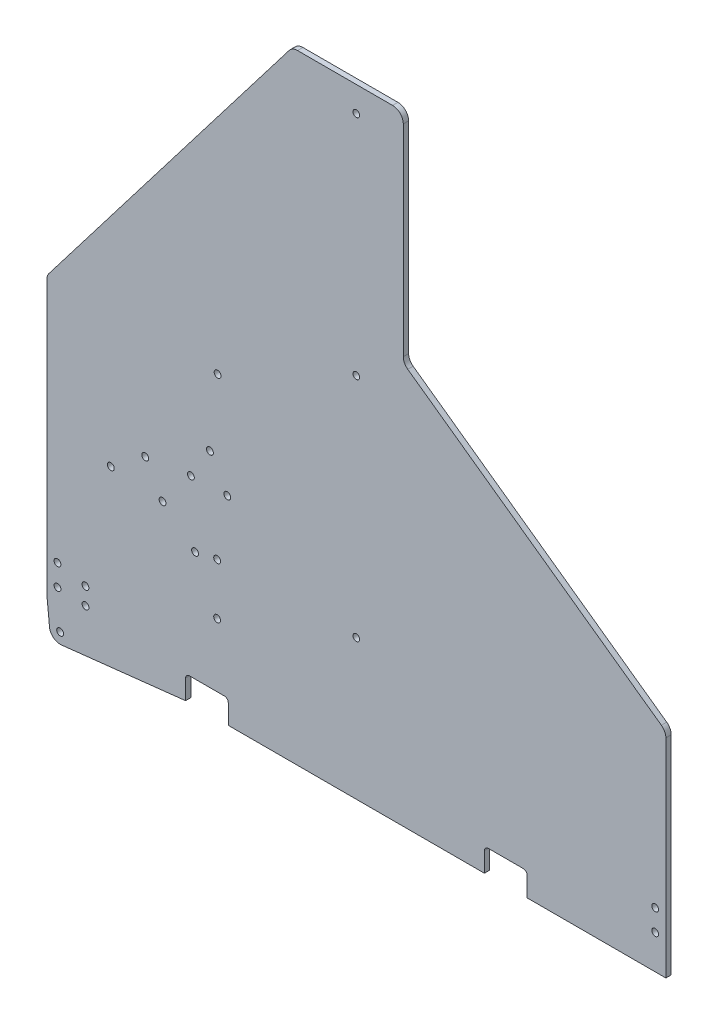
SolidWorks part; units mm, degrees
ref_plane "Front Plane" through (0, 0, 0) normal (0, 0, 1) x (1, 0, 0)
ref_plane "Top Plane" through (0, 0, 0) normal (0, 1, 0) x (1, 0, 0)
ref_plane "Right Plane" through (0, 0, 0) normal (1, 0, 0) x (0, 0, -1)
sketch "Sketch1" plane through (0, 0, 0) normal (0, 0, 1) x (1, 0, 0)
  line L0 (82.55, -20.32) -> (82.55, -6.35)
  line L2 (0, 0) -> (0, 157.48)
  line L4 (368.3, -20.32) -> (368.3, 106.68)
  line L5 (82.55, -6.35) -> (107.95, -6.35)
  line L6 (107.95, -6.35) -> (107.95, -20.32)
  line L7 (107.95, -20.32) -> (260.35, -20.32)
  line L8 (260.35, -20.32) -> (260.35, -6.35)
  line L9 (260.35, -6.35) -> (285.75, -6.35)
  line L10 (285.75, -6.35) -> (285.75, -20.32)
  line L11 (285.75, -20.32) -> (368.3, -20.32)
  line L12 (361.95, 12.7) -> (368.3, 12.7) construction
  line L13 (0, 0) -> (6.35, 0) construction
  line L14 (0.0315, -6.9818) -> (1.619, -22.8568)
  line L15 (8.6391, -28.5361) -> (82.55, -20.32)
  line L16 (0, 0) -> (0, -6.35)
  line L17 (85.725, 97.155) -> (82.9754, 95.5675) construction
  line L18 (97.0634, 115.6163) -> (58.5686, 93.3913) construction
  line L19 (97.0634, 115.6163) -> (107.3822, 97.7437) construction
  line L20 (58.5686, 93.3913) -> (68.8873, 75.5187) construction
  line L21 (107.3822, 97.7437) -> (68.8873, 75.5187) construction
  line L22 (97.0634, 115.6163) -> (68.8873, 75.5187) construction
  line L23 (58.5686, 93.3913) -> (107.3822, 97.7437) construction
  line L24 (7.9375, -22.225) -> (88.2169, 59.1366) construction
  line L25 (184.15, 62.98) -> (184.15, 197.98) construction
  line L26 (184.15, 197.98) -> (184.15, 332.98) construction
  line L27 (355.6, 335.28) -> (330.2, 335.28) construction
  line L28 (330.2, 335.28) -> (330.2, 220.98) construction
  line L29 (330.2, 220.98) -> (355.6, 220.98) construction
  line L30 (355.6, 220.98) -> (355.6, 335.28) construction
  line L31 (184.15, 347.98) -> (184.15, 269.4703) construction
  line L32 (12.7, 335.28) -> (38.1, 335.28) construction
  line L33 (38.1, 335.28) -> (38.1, 220.98) construction
  line L34 (12.7, 220.98) -> (12.7, 335.28) construction
  line L35 (38.1, 220.98) -> (12.7, 220.98) construction
  line L36 (146.05, 347.98) -> (184.15, 347.98)
  line L37 (184.15, 347.98) -> (146.05, 347.98)
  line L38 (184.15, 347.98) -> (212.09, 347.98)
  line L39 (348.5362, 347.98) -> (413.4623, 347.98)
  line L40 (348.5362, 347.98) -> (-141.0713, 347.98) construction
  line L42 (146.05, 347.98) -> (0, 157.48)
  line L44 (212.09, 347.98) -> (212.09, 218.44)
  line L45 (212.09, 218.44) -> (368.3, 106.68)
  circle A0 centre (6.35, 0) radius 2.032
  circle A1 centre (6.35, 12.7) radius 2.032
  circle A2 centre (361.95, 0) radius 2.032
  circle A3 centre (361.95, 12.7) radius 2.032
  arc A5 (1.619, -22.8568) -> (8.6391, -28.5361) centre (7.9375, -22.225) ccw
  circle A6 centre (7.9375, -22.225) radius 2.032
  arc A7 (0, -6.35) -> (0.0315, -6.9818) centre (6.35, -6.35) ccw
  circle A8 centre (38.1, 78.105) radius 2.032
  circle A9 centre (85.725, 97.155) radius 2.032
  circle A10 centre (58.5686, 93.3913) radius 2.032
  circle A11 centre (68.8873, 75.5187) radius 2.032
  circle A12 centre (107.3822, 97.7437) radius 2.032
  circle A13 centre (97.0634, 115.6163) radius 2.032
  circle A14 centre (88.2169, 59.1366) radius 2.032
  circle A15 centre (184.15, 62.98) radius 2
  circle A16 centre (184.15, 197.98) radius 2
  circle A17 centre (184.15, 332.98) radius 2
  circle A18 centre (63.5, 316.23) radius 2.032
  circle A19 centre (101.6, 157.48) radius 2.032
  circle A20 centre (355.6, 335.28) radius 2.032
  circle A21 centre (330.2, 335.28) radius 2.032
  circle A22 centre (355.6, 220.98) radius 2.032
  circle A23 centre (330.2, 220.98) radius 2.032
  circle A24 centre (12.7, 335.28) radius 2.032
  circle A25 centre (38.1, 335.28) radius 2.032
  circle A26 centre (12.7, 220.98) radius 2.032
  circle A27 centre (38.1, 220.98) radius 2.032
  point P82 (184.15, 347.98)
  dimension "D6" = 4.064
  dimension "D10" = 6.35
  dimension "D11" = 4.064
  dimension "D17" = 38.1
  dimension "D27" = 4
  dimension "D31" = 4.064
  dimension "D32" = 38.1
  dimension "D36" = 4.064
  dimension "D2" = 127
  dimension "D3" = 13.97
  dimension "D4" = 25.4
  dimension "D5" = 152.4
  dimension "D7" = 12.7
  dimension "D8" = 6.35
  dimension "D9" = 20.32
  dimension "D12" = 22.225
  dimension "D13" = 1.5875
  dimension "D14" = 82.55
  dimension "D15" = 368.3
  dimension "D16" = 6.35
  dimension "D18" = 98.425
  dimension "D19" = 47.625
  dimension "D20" = 19.05
  dimension "D21" = 3.175
  dimension "D22" = 60
  dimension "D23" = 20.6375
  dimension "D24" = 44.45
  dimension "D25" = 38.1
  dimension "D26" = 114.3
  dimension "D28" = 135
  dimension "D29" = 12.7
  dimension "D30" = 15
  dimension "D33" = 63.5
  dimension "D34" = 27.94
  dimension "D35" = 101.6
  dimension "D37" = 114.3
  dimension "D38" = 25.4
  dimension "D39" = 12.7
  dimension "D40" = 157.48
  dimension "D41" = 129.54
  dimension "D42" = 368.3
extrude "Boss-Extrude1" add sketch "Sketch1" along normal blind 3.175 contours L16 A7 L14 A5 L15 L0 L5 L6 L7 L8 L9 L10 L11 L4 L42 L2 A19 A17 A16 A15 A14 A13 A12 A11 A10 A9 A8 A0 A1 A2 A3 A6 region at (168.3767, 118.6221, 0)
fillet "Fillet1" radius 2.286 4 edges at (285.75, -6.35, 1.5875) (107.95, -6.35, 1.5875) (260.35, -6.35, 1.5875) (82.55, -6.35, 1.5875)
fillet "Fillet2" radius 6.35 5 edges at (0, 157.48, 1.5875) (212.09, 347.98, 1.5875) (212.09, 218.44, 1.5875) (368.3, 106.68, 1.5875) (146.05, 347.98, 1.5875)
sketch "Sketch2" plane through (0, 0, 0) normal (0, 0, -1) x (-1, 0, 0)
  circle A0 centre (-101.3398, 61.8475) radius 2.032 construction
  circle A1 centre (-101.3398, 31.3675) radius 2.032 construction
  circle A2 centre (-23.012, 8.964) radius 2.032 construction
  circle A3 centre (-23.012, -1.196) radius 2.032 construction
  circle A4 centre (-101.3398, 61.8475) radius 2.032
  circle A5 centre (-101.3398, 31.3675) radius 2.032
  circle A6 centre (-23.012, 8.964) radius 2.032
  circle A7 centre (-23.012, -1.196) radius 2.032
extrude "Cut-Extrude1" cut sketch "Sketch2" against normal through all
